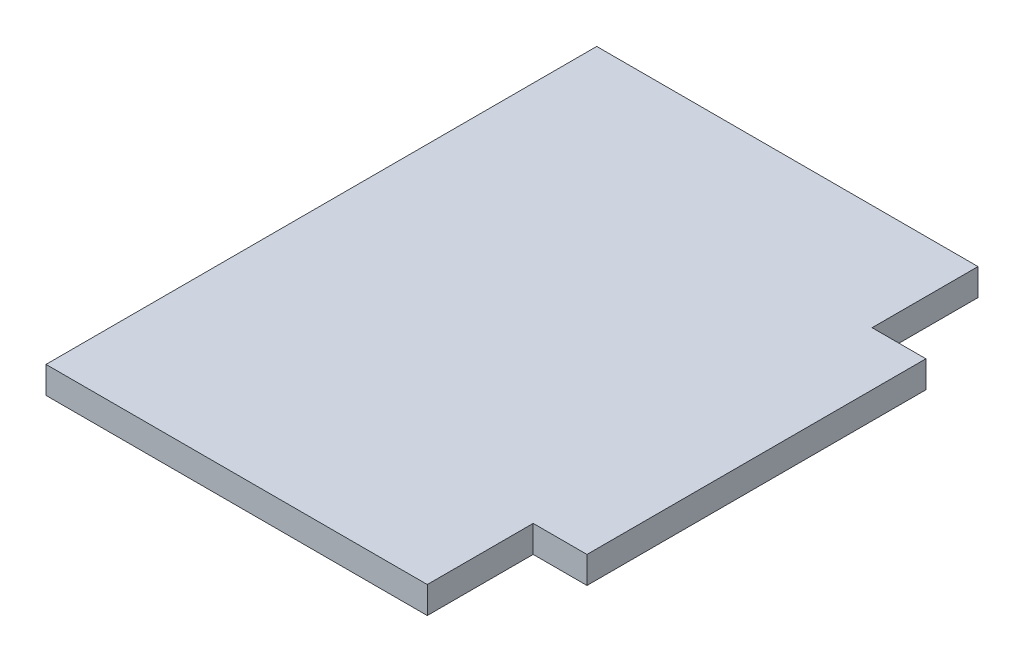
SolidWorks part; units mm, degrees
ref_plane "Front Plane" through (0, 0, 0) normal (0, 0, 1) x (1, 0, 0)
ref_plane "Top Plane" through (0, 0, 0) normal (0, 1, 0) x (1, 0, 0)
ref_plane "Right Plane" through (0, 0, 0) normal (1, 0, 0) x (0, 0, -1)
sketch "Sketch1" plane through (0, 0, 0) normal (0, 1, 0) x (1, 0, 0)
  line L0 (-22.5, 12.5) -> (22.5, 12.5)
  line L1 (22.5, 12.5) -> (22.5, 0)
  line L2 (22.5, 0) -> (28.85, 0)
  line L3 (28.85, 0) -> (28.85, -40)
  line L4 (28.85, -40) -> (22.5, -40)
  line L5 (22.5, -40) -> (22.5, -52.5)
  line L6 (22.5, -52.5) -> (-22.5, -52.5)
  line L7 (-22.5, -52.5) -> (-22.5, -40)
  line L8 (-22.5, -40) -> (-28.85, -40)
  line L9 (-28.85, -40) -> (-28.85, 0)
  line L10 (-28.85, 0) -> (-22.5, 0)
  line L11 (-22.5, 0) -> (-22.5, 12.5)
  line L12 (-22.5, 0) -> (-22.5, -40) construction
  point P11 (0, 12.5)
  point P14 (-28.85, -20)
  dimension "D1" = 6.35
  dimension "D2" = 40
  dimension "D3" = 45
  dimension "D4" = 65
extrude "Boss-Extrude1" add sketch "Sketch1" along normal blind 3.175 contours L11 L12 L7 L6 L5 L4 L3 L2 L1 L0 region at (2.0514, 0, 20)
equation "\"length\" = 65mm"
equation "\"w_mach\"= 45mm"
equation "\"w_tab\" = 40mm"
equation "\"t_wood\"= 0.125in"
equation "\"t_side\"= 0.25in"
equation "\"D1@Sketch1\"=\"t_side\""
equation "\"D2@Sketch1\"=\"w_tab\""
equation "\"D3@Sketch1\"=\"w_mach\""
equation "\"D4@Sketch1\"=\"length\""
equation "\"D1@Boss-Extrude1\"=\"t_wood\""
